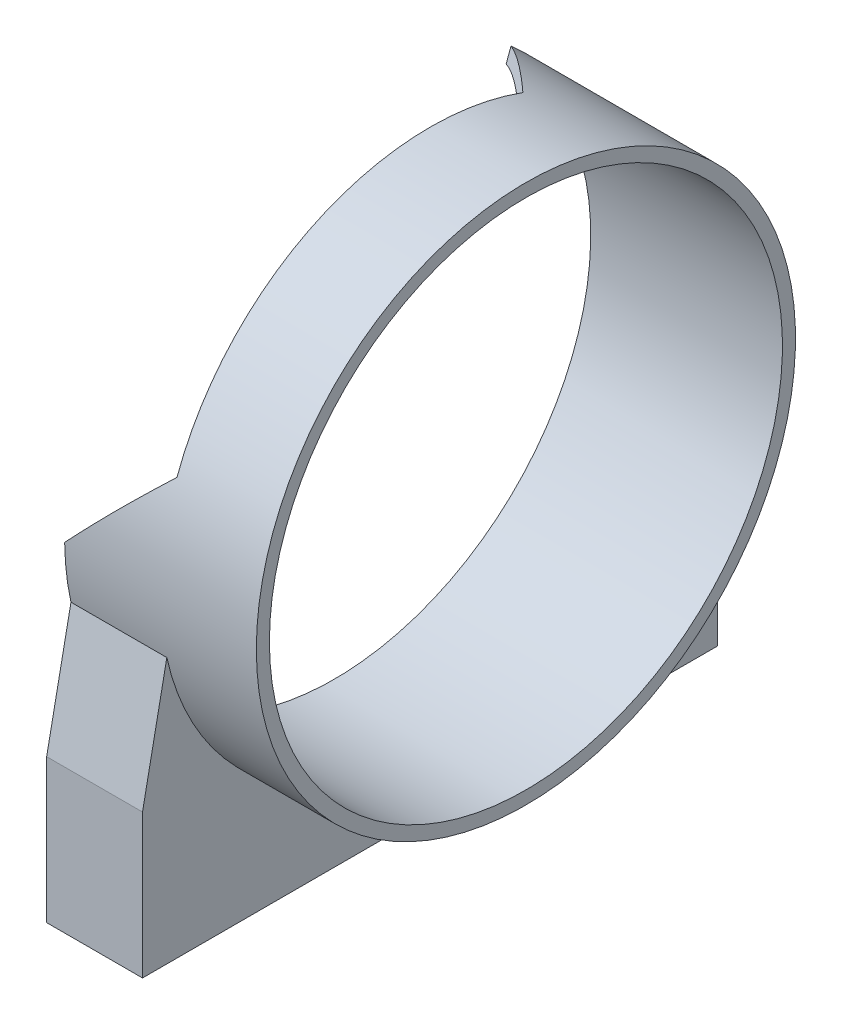
SolidWorks part; units mm, degrees
ref_plane "前视基准面" through (0, 0, 0) normal (0, 0, 1) x (1, 0, 0)
ref_plane "上视基准面" through (0, 0, 0) normal (0, 1, 0) x (1, 0, 0)
ref_plane "右视基准面" through (0, 0, 0) normal (1, 0, 0) x (0, 0, -1)
sketch "草图1" plane through (0, 0, 0) normal (1, 0, 0) x (0, 0, -1)
  line L0 (0, 0) -> (-21, 0)
  line L1 (-21, 0) -> (-21, 27)
  line L2 (0, 0) -> (0, 6)
  line L3 (-21, 0) -> (-24, 0)
  line L4 (-24, 0) -> (-24, 12)
  line L5 (-24, 12) -> (-21, 27)
  circle A0 centre (0, 27) radius 21.41
extrude "凸台-拉伸1" add sketch "草图1" against normal blind 8 contours L1 L0 L2 | L5 L4 L3 L1 region at (0, 5.9313, 13.0033) region at (0, 10.0337, 22.3236)
ref_plane "基准面1" through (0, 0, 0) normal (0, 0, -1) x (-1, 0, 0)
mirror "镜向1" about plane through (0, 0, 0) normal (0, 0, -1) of "凸台-拉伸1"
hole_wizard "大小mm 暗销孔1" positions "草图3" profile "草图4" hole size "Ø4.0" standard "GB"
sketch "草图3" plane through (0, 0, 0) normal (0, -1, 0) x (-1, 0, 0)
  line L3 (5, 0) -> (5, 21)
  line L4 (5, 0) -> (5, -21)
  line L5 (5, 0) -> (8, 0)
  line L6 (8, 24) -> (8, -24) construction
  point P8 (5, 21)
  point P18 (5, -21)
sketch "草图4" plane through (-5, 0, -21) normal (1, 0, 0) x (0, 0, -1)
  line L0 (0, 0) -> (0, 13.2017)
  line L1 (0, 13.2017) -> (2, 12)
  line L2 (2, 12) -> (2, 0)
  line L5 (2, 0) -> (0, 0)
  line L10 (0, 13.2017) -> (-2, 12) construction
  line L11 (0, -6.35) -> (0, 107.95) construction
  dimension "孔直径" = 4
  dimension "孔深度" = 12
  dimension "导头角度" = 118
sketch "草图5" plane through (-8, 0, 0) normal (-1, 0, 0) x (0, 0, 1)
  circle A0 centre (0, 27) radius 21.41
  circle A1 centre (0, 27) radius 22.5
extrude "凸台-拉伸2" add sketch "草图5" against normal blind 16
sketch "草图6" plane through (-8, 0, 0) normal (-1, 0, 0) x (0, 0, 1)
  line L0 (0, 27) -> (-12.8087, 61.9126)
  line L1 (0, 27) -> (29.3075, 37.7523)
  line L2 (29.3075, 37.7523) -> (-12.8087, 61.9126)
extrude "切除-拉伸1" cut sketch "草图6" against normal blind 8
chamfer "倒角1" distance 8 angle 45 2 edges at (-8, 34.5619, 20.6116) (-8, 47.6116, -7.5619)
